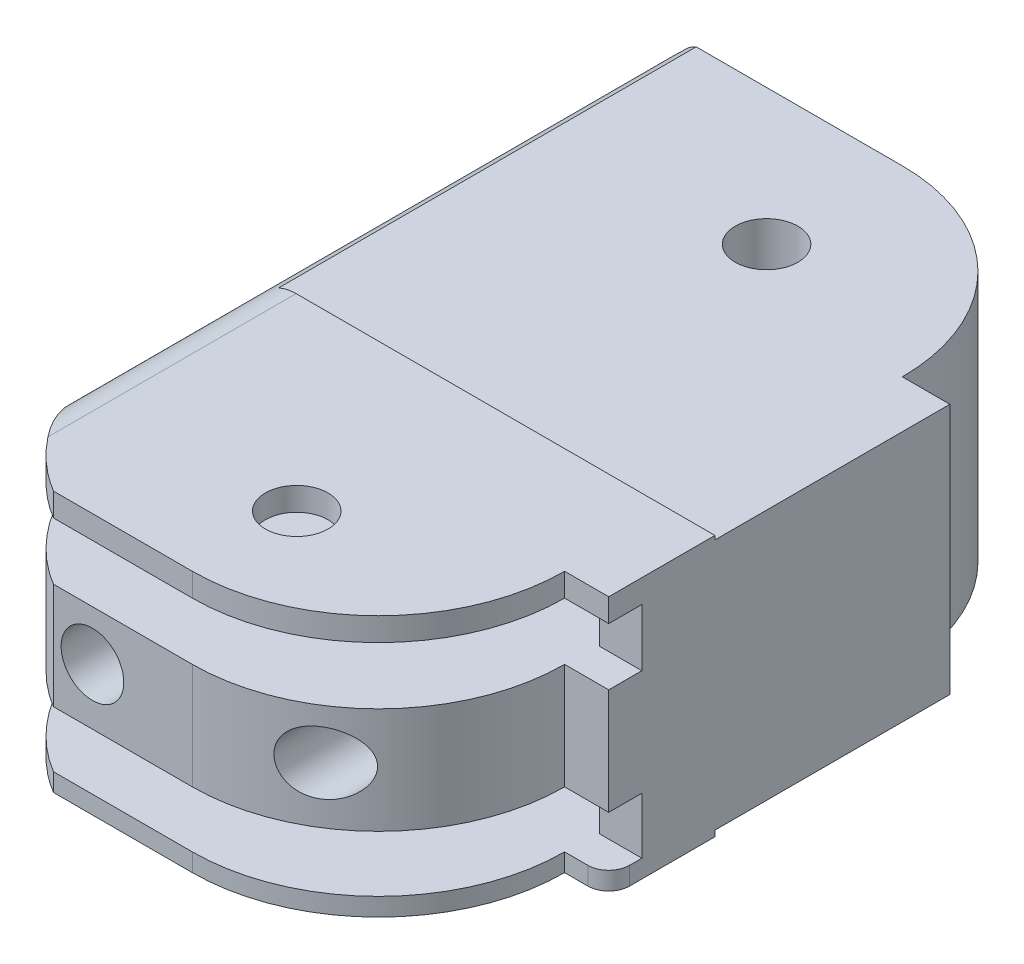
SolidWorks part; units mm, degrees
ref_plane "Front Plane" through (0, 0, 0) normal (0, 0, 1) x (1, 0, 0)
ref_plane "Top Plane" through (0, 0, 0) normal (0, 1, 0) x (1, 0, 0)
ref_plane "Right Plane" through (0, 0, 0) normal (1, 0, 0) x (0, 0, -1)
sketch "Sketch1" plane through (0, 0, 0) normal (0, 0, 1) x (1, 0, 0)
  line L0 (-24.2561, -24.0702) -> (-22.0061, -24.0702) construction
  line L1 (-24.2561, -17.8202) -> (-2.2017, -17.8202)
  line L2 (-24.2561, -17.8202) -> (-24.2561, -30.3202)
  line L3 (-24.2561, -30.3202) -> (-2.2017, -30.3202)
  line L4 (-2.2017, -17.8202) -> (-2.2017, -30.3202)
  line L5 (-2.2017, -24.0702) -> (-4.4517, -24.0702) construction
  line L6 (-22.0061, -24.0702) -> (-22.0061, -30.3202) construction
  line L7 (-4.4517, -24.0702) -> (-4.4517, -30.3202) construction
extrude "Boss-Extrude1" add sketch "Sketch1" along normal blind 34
sketch "Sketch2" plane through (0, -30.3202, 0) normal (0, -1, 0) x (1, 0, 0)
  line L0 (-4.3151, 25.0862) -> (-2.2017, 25.0862)
  line L1 (-24.2561, 0) -> (-2.2017, 0) construction
  line L2 (-13.2289, 0) -> (-13.2289, 8.75) construction
  line L4 (-24.2561, 34) -> (-24.2561, 0) construction
  line L5 (-4.4789, 8.75) -> (-2.2017, 8.75)
  line L6 (-2.2017, 34) -> (-2.2017, 0) construction
  line L7 (-13.2289, 34) -> (-13.2289, 29) construction
  line L8 (-24.2561, 34) -> (-2.2017, 34) construction
  line L11 (-13.2289, 8.75) -> (-13.2289, 6.5) construction
  line L12 (-24.2561, 0) -> (-2.2017, 0) construction
  arc A1 (-13.2289, 0) -> (-4.4789, 8.75) centre (-13.2289, 8.75) ccw
  circle A4 centre (-13.2289, 6.5) radius 1.5
  arc A6 (-4.3151, 25.0862) -> (-13.2289, 34) centre (-13.2289, 25.0862) ccw
  circle A8 centre (-13.2289, 29) radius 1.5
  spline S0 degree 3 poles (-2.2017, 8.75) (5.3921, 3.8803) (-0.7771, -4.5233) (-17.1743, -10.6233) (-34.8214, -0.026) (-24.2561, 8.75) knots 0 0 0 0 0.283273 0.504245 1 1 1 1
  spline S1 degree 3 poles (-24.2561, 25.4586) (-35.656, 36.5403) (-13.0069, 52.2851) (9.3223, 36.3385) (-2.2017, 25.0862) knots 0 0 0 0 0.496842 1 1 1 1
  spline S2 degree 1 poles (-13.2289, 0) (-23.4906, 0) knots 0 0 1 1
  spline S3 degree 2 poles (-23.4906, 0) (-24.9665, 4.2378) (-24.2561, 8.75) knots 0 0 0 1 1 1
  spline S4 degree 3 poles (-13.2289, 34) (-19.0864, 37.4223) (-24.8857, 30.869) (-24.2561, 25.4586) knots 0 0 0 0 1 1 1 1
extrude "Cut-Extrude1" cut sketch "Sketch2" against normal blind 15 and the other way blind 10
fillet "Fillet3" radius 2 4 edges at (-24.2561, -17.8202, 15.0641) (-24.2561, -30.3202, 15.0641) (-24.2561, -24.0702, 3.0015) (-24.2561, -24.0702, 27.1267)
ref_plane "Plane1" through (0, 0, 0) normal (0, 0, 1) x (1, 0, 0)
sketch "Sketch5" plane through (0, 0, 0) normal (0, 0, 1) x (1, 0, 0)
  line L0 (-2.2017, -24.0702) -> (-8.4468, -24.0702) construction
  line L1 (-2.2017, -30.3202) -> (-24.2561, -30.3202) construction
  line L2 (-2.2017, -30.3202) -> (-2.2017, -17.8202) construction
  line L3 (-2.2017, -17.8202) -> (-24.2561, -17.8202) construction
  line L4 (-24.2561, -30.3202) -> (-24.2561, -17.8202) construction
  line L5 (-24.2561, -24.0702) -> (-18.0111, -24.0702) construction
  circle A0 centre (-18.0111, -24.0702) radius 1.5
  circle A1 centre (-8.4468, -24.0702) radius 1.5
extrude "Cut-Extrude4" cut sketch "Sketch5" along normal through all
ref_plane "Plane5" through (0, 0, 38) normal (0, 0, 1) x (1, 0, 0)
sketch "Sketch16" plane through (0, 0, 38) normal (0, 0, 1) x (1, 0, 0)
  line L0 (-2.1959, -17.435) -> (-2.1959, -18.935) construction
  line L1 (-2.1959, -17.435) -> (-24.262, -17.435) construction
  line L2 (-2.1959, -17.435) -> (-2.1959, -30.958) construction
  line L3 (-2.1959, -30.958) -> (-24.262, -30.958) construction
  line L4 (-24.262, -17.435) -> (-24.262, -30.958) construction
  line L5 (-2.1959, -17.435) -> (-24.262, -30.958) construction
  line L6 (-2.1959, -30.958) -> (-24.262, -17.435) construction
  line L7 (-2.1959, -30.958) -> (-2.1959, -29.458) construction
  line L8 (-13.2289, -21.681) -> (-13.2289, -24.1965) construction
  line L9 (-2.1959, -18.935) -> (-24.262, -18.935)
  line L10 (-2.1959, -18.935) -> (-2.1959, -21.681)
  line L11 (-2.1959, -21.681) -> (-24.262, -21.681)
  line L12 (-24.262, -18.935) -> (-24.262, -21.681)
  line L13 (-2.1959, -18.935) -> (-24.262, -21.681) construction
  line L14 (-2.1959, -21.681) -> (-24.262, -18.935) construction
  line L15 (-2.1959, -29.458) -> (-24.262, -29.458)
  line L16 (-2.1959, -29.458) -> (-2.1959, -26.7619)
  line L17 (-2.1959, -26.7619) -> (-24.262, -26.7619)
  line L18 (-24.262, -29.458) -> (-24.262, -26.7619)
  line L19 (-2.1959, -29.458) -> (-24.262, -26.7619) construction
  line L20 (-2.1959, -26.7619) -> (-24.262, -29.458) construction
  line L21 (-13.2289, -24.1965) -> (-13.2289, -26.7619) construction
  point P4 (-13.2289, -24.1965)
  point P10 (-13.2289, -20.308)
  point P14 (-13.2289, -28.1099)
extrude "Cut-Extrude6" cut sketch "Sketch16" against normal blind 14.5
fillet "Fillet4" radius 1 1 edges at (-2.2017, -29.8891, 25.0862)
sketch "Sketch17" plane through (0, 0, 23.5) normal (0, 0, 1) x (1, 0, 0)
  line L0 (-2.2017, -18.935) -> (-24.0496, -18.935) construction
  line L1 (-4.2186, -18.935) -> (-22.4714, -18.935)
  line L2 (-4.2186, -18.935) -> (-4.2186, -21.681)
  line L3 (-4.2186, -21.681) -> (-22.4714, -21.681)
  line L4 (-22.4714, -18.935) -> (-22.4714, -21.681)
  line L5 (-4.2186, -18.935) -> (-22.4714, -21.681) construction
  line L6 (-4.2186, -21.681) -> (-22.4714, -18.935) construction
  line L7 (-24.2561, -21.681) -> (-2.2017, -21.681) construction
  line L8 (-2.2017, -26.7619) -> (-24.2561, -26.7619) construction
  line L9 (-22.4714, -26.7619) -> (-4.2186, -26.7619)
  line L10 (-22.4714, -26.7619) -> (-22.4714, -29.458)
  line L11 (-22.4714, -29.458) -> (-4.2186, -29.458)
  line L12 (-4.2186, -26.7619) -> (-4.2186, -29.458)
  line L13 (-22.4714, -26.7619) -> (-4.2186, -29.458) construction
  line L14 (-22.4714, -29.458) -> (-4.2186, -26.7619) construction
  line L15 (-23.901, -29.458) -> (-2.2017, -29.458) construction
  point P4 (-13.345, -20.308)
  point P13 (-13.345, -28.1099)
extrude "Cut-Extrude7" cut sketch "Sketch17" against normal blind 5
sketch "Sketch18" plane through (0, 0, 0) normal (0, 0, 1) x (1, 0, 0)
  line L1 (-24.958, -17.4016) -> (-0.6241, -17.4016)
  line L2 (-24.958, -17.4016) -> (-24.958, -18.007)
  line L3 (-24.958, -18.007) -> (-0.6241, -18.007)
  line L4 (-0.6241, -17.4016) -> (-0.6241, -18.007)
  line L5 (-24.958, -17.4016) -> (-0.6241, -18.007) construction
  line L6 (-24.958, -18.007) -> (-0.6241, -17.4016) construction
  line L7 (-24.958, -30.7703) -> (-0.6241, -30.7703)
  line L8 (-24.958, -30.7703) -> (-24.958, -30.0444)
  line L9 (-24.958, -30.0444) -> (-0.6241, -30.0444)
  line L10 (-0.6241, -30.7703) -> (-0.6241, -30.0444)
  line L11 (-24.958, -30.7703) -> (-0.6241, -30.0444) construction
  line L12 (-24.958, -30.0444) -> (-0.6241, -30.7703) construction
  point P4 (-12.791, -17.7043)
  point P9 (-12.791, -30.4074)
extrude "Cut-Extrude8" cut sketch "Sketch18" along normal blind 20
